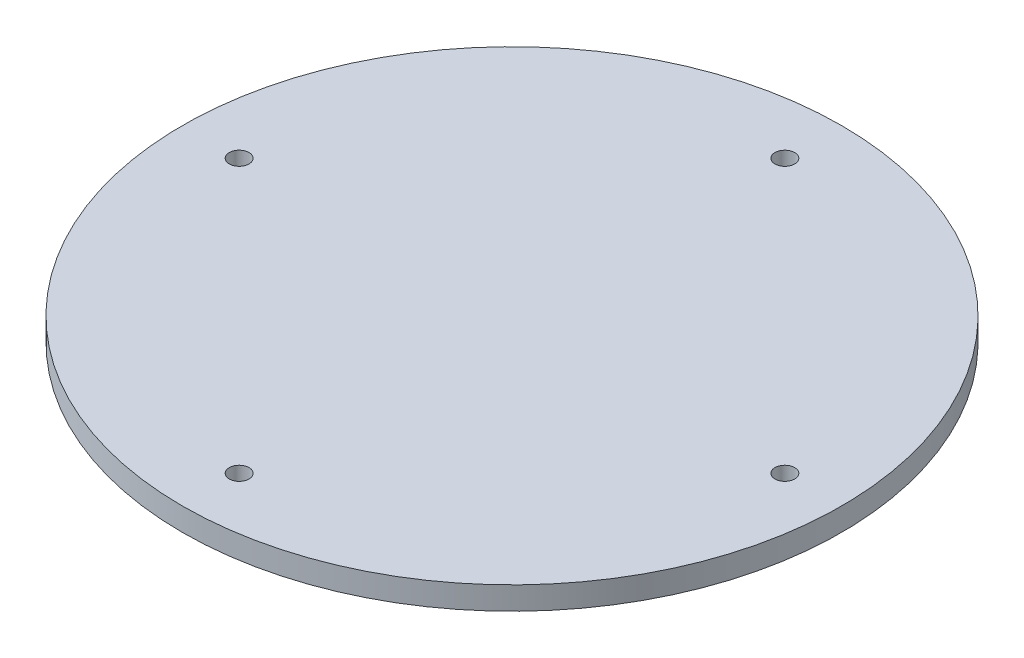
SolidWorks part; units mm, degrees
ref_plane "Plan de face" through (0, 0, 0) normal (0, 0, 1) x (1, 0, 0)
ref_plane "Plan de dessus" through (0, 0, 0) normal (0, 1, 0) x (1, 0, 0)
ref_plane "Plan de droite" through (0, 0, 0) normal (1, 0, 0) x (0, 0, -1)
sketch "Esquisse1" plane through (0, 0, 0) normal (0, 1, 0) x (1, 0, 0)
  circle A0 centre (0, 0) radius 32.53
  dimension "D1" = 65.06
extrude "Boss.-Extru.1" add sketch "Esquisse1" against normal blind 8.03
sketch "Esquisse2" plane through (0, 0, 0) normal (0, 1, 0) x (1, 0, 0)
  circle A0 centre (0, 0) radius 49.956
  dimension "D1" = 99.912
extrude "Boss.-Extru.2" add sketch "Esquisse2" along normal blind 3.47
sketch "Esquisse3" plane through (0, 0, 0) normal (0, 1, 0) x (1, 0, 0)
  line L0 (0, -49.956) -> (0, -41.356) construction
  line L1 (-41.3605, 0) -> (-49.956, 0) construction
  line L2 (39.856, 0) -> (49.956, 0) construction
  line L3 (-36.5348, -0.0615) -> (-44.3337, -0.0615) construction
  line L4 (0, -49.956) -> (0, -41.356) construction
  line L5 (49.956, 0) -> (41.356, 0) construction
  line L6 (0, 49.956) -> (0, 41.356) construction
  line L7 (0, 41.356) -> (0, 49.956) construction
  circle A0 centre (0, 0) radius 49.956 construction
  circle A1 centre (-41.3605, 0) radius 1.5
  circle A2 centre (0, -41.356) radius 1.5
  circle A3 centre (0, 41.356) radius 1.5
  circle A4 centre (41.356, 0) radius 1.5
  dimension "D1" = 8.5955
  dimension "D2" = 8.6
  dimension "D3" = 8.6
  dimension "D4" = 8.6
extrude "Enlèv. mat.-Extru.1" cut sketch "Esquisse3" along normal blind 5
